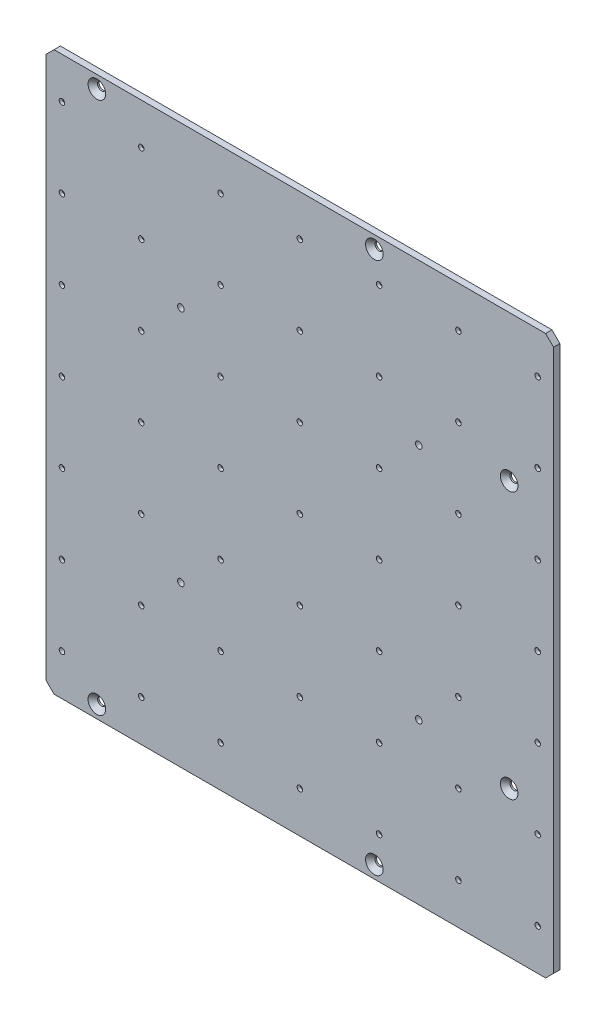
SolidWorks part; units mm, degrees
material "ABS"
ref_plane "Front Plane" through (0, 0, 0) normal (0, 0, 1) x (1, 0, 0)
ref_plane "Top Plane" through (0, 0, 0) normal (0, 1, 0) x (1, 0, 0)
ref_plane "Right Plane" through (0, 0, 0) normal (1, 0, 0) x (0, 0, -1)
sketch "Sketch1" plane through (0, 0, 0) normal (0, 0, 1) x (1, 0, 0)
  line L0 (-155, 176) -> (-160, 171)
  line L1 (155, 176) -> (-155, 176)
  line L2 (160, 171) -> (160, -171)
  line L3 (155, -176) -> (-155, -176)
  line L4 (-160, 171) -> (-160, -171)
  line L5 (160, 176) -> (-160, -176) construction
  line L6 (160, -176) -> (-160, 176) construction
  line L7 (-155, -176) -> (-160, -171)
  line L8 (160, -171) -> (155, -176)
  line L9 (160, 171) -> (155, 176)
  point P0 (0, 0)
  dimension "D1" = 320
  dimension "D2" = 352
extrude "Base" add sketch "Sketch1" along normal blind 4
sketch "Sketch2" plane through (0, 0, 4) normal (0, 0, 1) x (1, 0, 0)
  line L0 (-40.5, -18.9167) -> (-40.5, 0) construction
  line L1 (-40.5, 0) -> (-17.5548, 0) construction
  line L3 (132, -168) -> (-213, -168) construction
  line L5 (132, -168) -> (132, 168) construction
  line L8 (132, 168) -> (-213, 168) construction
  line L9 (-213, -168) -> (-213, 168) construction
  line L10 (132, -168) -> (-213, 168) construction
  line L11 (132, 168) -> (-213, -168) construction
  circle A5 centre (-128, 168) radius 2.55
  circle A8 centre (47, 168) radius 2.55
  circle A9 centre (132, 84) radius 2.55
  circle A10 centre (132, -84) radius 2.55
  circle A11 centre (47, -168) radius 2.55
  circle A12 centre (-128, -168) radius 2.55
  point P16 (-40.5, 0)
  dimension "D5" = 345
  dimension "D2" = 175
  dimension "D7" = 5.1
  dimension "D1" = 168
  dimension "D3" = 40.5
  dimension "D6" = 336
extrude "MountHoles" cut sketch "Sketch2" against normal blind 8
chamfer "ChamferForMount" distance 3 angle 45 6 edges at (-125.45, 168, 4) (49.55, 168, 4) (134.55, 84, 4) (134.55, -84, 4) (49.55, -168, 4) (-125.45, -168, 4)
sketch "Sketch5" plane through (0, 0, 4) normal (0, 0, 1) x (1, 0, 0)
  line L0 (-147.5, 0) -> (147.5, 0) construction
  line L1 (0, 0) -> (0, -28.8331) construction
  circle A0 centre (50, 0) radius 1.75
  circle A1 centre (100, 0) radius 1.75
  circle A2 centre (150, 0) radius 1.75
  circle A3 centre (50, 50) radius 1.75
  circle A4 centre (100, 50) radius 1.75
  circle A5 centre (150, 50) radius 1.75
  circle A6 centre (50, 100) radius 1.75
  circle A7 centre (100, 100) radius 1.75
  circle A8 centre (150, 100) radius 1.75
  circle A9 centre (50, 150) radius 1.75
  circle A10 centre (0, 0) radius 1.75
  circle A11 centre (100, 150) radius 1.75
  circle A12 centre (150, 150) radius 1.75
  circle A13 centre (0, 50) radius 1.75
  circle A14 centre (0, 100) radius 1.75
  circle A15 centre (0, 0) radius 1.75
  circle A16 centre (0, 150) radius 1.75
  circle A17 centre (0, -150) radius 1.75
  circle A18 centre (0, -100) radius 1.75
  circle A19 centre (0, -50) radius 1.75
  circle A20 centre (150, -150) radius 1.75
  circle A21 centre (100, -150) radius 1.75
  circle A22 centre (50, -150) radius 1.75
  circle A23 centre (150, -100) radius 1.75
  circle A24 centre (100, -100) radius 1.75
  circle A25 centre (50, -100) radius 1.75
  circle A26 centre (150, -50) radius 1.75
  circle A27 centre (100, -50) radius 1.75
  circle A28 centre (50, -50) radius 1.75
  circle A29 centre (-150, 0) radius 1.75
  circle A30 centre (-100, 0) radius 1.75
  circle A31 centre (-50, 0) radius 1.75
  circle A32 centre (-50, -50) radius 1.75
  circle A33 centre (-100, -50) radius 1.75
  circle A34 centre (-150, -50) radius 1.75
  circle A35 centre (-50, -100) radius 1.75
  circle A36 centre (-100, -100) radius 1.75
  circle A37 centre (-150, -100) radius 1.75
  circle A38 centre (-50, -150) radius 1.75
  circle A39 centre (-100, -150) radius 1.75
  circle A40 centre (-150, -150) radius 1.75
  circle A41 centre (-150, 150) radius 1.75
  circle A42 centre (-100, 150) radius 1.75
  circle A43 centre (-50, 150) radius 1.75
  circle A44 centre (-150, 100) radius 1.75
  circle A45 centre (-100, 100) radius 1.75
  circle A46 centre (-50, 100) radius 1.75
  circle A47 centre (-150, 50) radius 1.75
  circle A48 centre (-100, 50) radius 1.75
  circle A49 centre (-50, 50) radius 1.75
  circle A65 centre (0, 0) radius 1.75
  circle A110 centre (0, 0) radius 1.75
  circle A155 centre (0, 0) radius 1.75
  dimension "D3" = 4
  dimension "D1" = 3.5
  dimension "D2" = 4
  dimension "D6" = 4
  dimension "D7" = 4
extrude "AirHoldHoles" cut sketch "Sketch5" against normal through all contours A40 | A39 | A38 | A17 | A22 | A21 | A20 | A23 | A26 | A2 | A5 | A8 | A12 | A11 | A9 | A16 | A43 | A42 | A41 | A44 | A47 | A29 | A34 | A37 | A36 | A35 | A18 | A25 | A24 | A27 | A1 | A4 | A6 | A14 | A46 | A45 | A48 | A30 | A33 | A32 | A19 | A28 | A0 | A3 | A13 | A49 | A31 | A10 | A4 | A7 region at (50, 0, 4) region at (100, 0, 4) region at (150, 0, 4) region at (50, 50, 4) region at (100, 50, 4) region at (150, 50, 4) region at (50, 100, 4) region at (150, 100, 4) region at (50, 150, 4) region at (0, 0, 4) region at (100, 150, 4) region at (150, 150, 4) region at (0, 50, 4) region at (0, 100, 4) region at (0, 150, 4) region at (0, -150, 4) region at (0, -100, 4) region at (0, -50, 4) region at (150, -150, 4) region at (100, -150, 4) region at (50, -150, 4) region at (150, -100, 4) region at (100, -100, 4) region at (50, -100, 4) region at (150, -50, 4) region at (100, -50, 4) region at (50, -50, 4) region at (-150, 0, 4) region at (-100, 0, 4) region at (-50, 0, 4) region at (-50, -50, 4) region at (-100, -50, 4) region at (-150, -50, 4) region at (-50, -100, 4) region at (-100, -100, 4) region at (-150, -100, 4) region at (-50, -150, 4) region at (-100, -150, 4) region at (-150, -150, 4) region at (-150, 150, 4) region at (-100, 150, 4) region at (-50, 150, 4) region at (-150, 100, 4) region at (-100, 100, 4) region at (-50, 100, 4) region at (-150, 50, 4) region at (-100, 50, 4) region at (-50, 50, 4)
sketch "Sketch6" plane through (0, 0, 4) normal (0, 0, 1) x (1, 0, 0)
  line L0 (-6.7475, 0) -> (0, 0) construction
  line L1 (0, 0) -> (0, -6.556) construction
  circle A0 centre (-75, -75) radius 2.1
  circle A1 centre (75, -75) radius 2.1
  circle A2 centre (75, 75) radius 2.1
  circle A3 centre (-75, 75) radius 2.1
  dimension "D1" = 4.2
  dimension "D2" = 75
  dimension "D3" = 75
extrude "ScrewHoldHoles" cut sketch "Sketch6" against normal through all
sketch "Sketch7" plane through (0, 0, 0) normal (0, 0, -1) x (-1, 0, 0)
  line L0 (160, 171) -> (160, -171) construction
  circle A0 centre (130, 0) radius 4
  dimension "D2" = 8
  dimension "D1" = 30
extrude "BlindFittingHole" cut sketch "Sketch7" against normal blind 2
sketch "Sketch8" plane through (0, 0, 0) normal (0, 0, -1) x (-1, 0, 0)
  line L0 (-150, 0) -> (150, 0) construction
  line L1 (150, 0) -> (150, -150) construction
  line L2 (150, 150) -> (150, 0) construction
  line L3 (-150, 50) -> (100, 50) construction
  line L4 (-150, 100) -> (100, 100) construction
  line L5 (-150, 150) -> (100, 150) construction
  line L6 (100, 150) -> (100, 0) construction
  line L7 (-150, -150) -> (100, -150) construction
  line L8 (100, -150) -> (100, 0) construction
  line L9 (-150, -50) -> (100, -50) construction
  line L10 (-150, -100) -> (100, -100) construction
  line L11 (100, 50) -> (130, 0) construction
  line L12 (130, 0) -> (100, -50) construction
  line L13 (-150, 148.25) -> (98.25, 148.25)
  line L14 (98.25, 148.25) -> (98.25, 0)
  line L15 (98.25, -148.25) -> (98.25, 0)
  line L16 (-150, -148.25) -> (98.25, -148.25)
  line L17 (-150, 98.25) -> (100, 98.25)
  line L18 (-150, 48.25) -> (99.0092, 48.25)
  line L19 (99.0092, 48.25) -> (127.9592, 0)
  line L20 (127.9592, 0) -> (99.0092, -48.25)
  line L21 (-150, -48.25) -> (99.0092, -48.25)
  line L22 (-150, -1.75) -> (150, -1.75)
  line L23 (-150, -101.75) -> (100, -101.75)
  line L24 (148.25, 0) -> (148.25, -150)
  line L25 (148.25, 150) -> (148.25, 0)
  line L26 (-150, 151.75) -> (101.75, 151.75)
  line L27 (101.75, 151.75) -> (101.75, 0)
  line L28 (101.75, -151.75) -> (101.75, 0)
  line L29 (-150, -151.75) -> (101.75, -151.75)
  line L30 (-150, 101.75) -> (100, 101.75)
  line L31 (-150, 51.75) -> (100.9908, 51.75)
  line L32 (100.9908, 51.75) -> (132.0408, 0)
  line L33 (132.0408, 0) -> (100.9908, -51.75)
  line L34 (-150, -51.75) -> (100.9908, -51.75)
  line L35 (-150, 1.75) -> (150, 1.75)
  line L36 (-150, -98.25) -> (100, -98.25)
  line L37 (151.75, 0) -> (151.75, -150)
  line L38 (151.75, 150) -> (151.75, 0)
  line L39 (-150, -151.75) -> (-150, -148.25)
  line L40 (-150, -101.75) -> (-150, -98.25)
  line L41 (-150, -48.25) -> (-150, -51.75)
  line L42 (-150, 1.75) -> (-150, -1.75)
  line L43 (-150, 51.75) -> (-150, 48.25)
  line L44 (-150, 101.75) -> (-150, 98.25)
  line L45 (-150, 98.25) -> (-149.8852, 98.2376)
  line L46 (-150, 151.75) -> (-150, 148.25)
  line L47 (148.25, 150) -> (151.75, 150)
  line L48 (148.25, -150) -> (151.75, -150)
  dimension "D1" = 1.75
  dimension "D2" = 1.75
extrude "Cut-Extrude6" cut sketch "Sketch8" against normal blind 2 contours L24 L48 L37 L38 L47 L25 | L35 L32 L33 L22 L24 L25 | L19 L35 L32 L27 | L35 L27 L28 L22 L20 L19 | L35 L19 L20 L22 L33 L32 | L33 L22 L20 L28 | L35 L14 L15 L22 L28 L27 | L14 L35 L27 L19 L18 | L35 L42 L22 L15 L14 | L20 L28 L22 L15 L21 | L15 L34 L33 L28 L20 L21 | L21 L41 L34 L15 | L39 L29 L28 L33 L34 L15 L16 | L40 L23 L15 L36 | L32 L31 L14 L18 L19 L27 | L31 L43 L18 L14 | L26 L46 L13 L14 L31 L32 L27 | L30 L44 L17 L14 region at (147.2865, 150, 0) region at (25.875, 100, 0) region at (-115.3755, 24.4592, 0) region at (-100.2505, 48.8283, 0) region at (25.875, 50, 0) region at (-99.9665, 24.1308, 0) region at (-139.8802, 0, 0) region at (-129.475, 0, 0) region at (-114.5939, 0, 0) region at (-100, 0, 0) region at (-150, 0, 0) region at (25.875, 0, 0) region at (-115.3755, -24.4592, 0) region at (-99.9665, -24.1308, 0) region at (-100.2505, -48.8283, 0) region at (-99.0365, -101.1174, 0) region at (25.875, -50, 0) region at (25.875, -100, 0)
